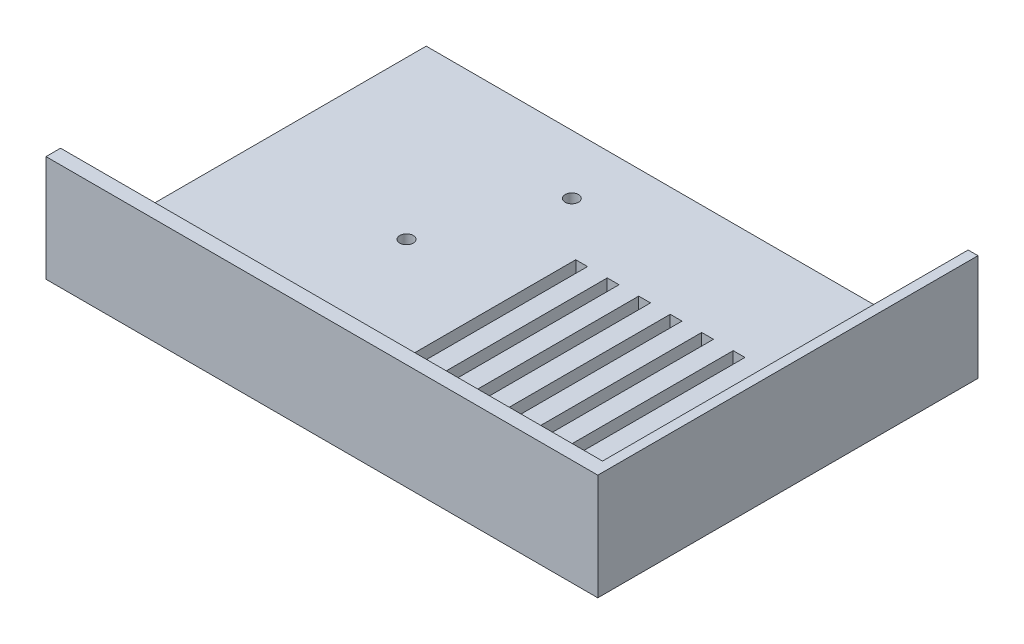
SolidWorks part; units mm, degrees
ref_plane "Front Plane" through (0, 0, 0) normal (0, 0, 1) x (1, 0, 0)
ref_plane "Top Plane" through (0, 0, 0) normal (0, 1, 0) x (1, 0, 0)
ref_plane "Right Plane" through (0, 0, 0) normal (1, 0, 0) x (0, 0, -1)
sketch "Sketch1" plane through (0, 0, 0) normal (0, 1, 0) x (1, 0, 0)
  line L1 (-140.2, -96.6) -> (140.2, -96.6)
  line L2 (-140.2, -96.6) -> (-140.2, 96.6)
  line L3 (-140.2, 96.6) -> (140.2, 96.6)
  line L4 (140.2, -96.6) -> (140.2, 96.6)
  line L5 (-140.2, -96.6) -> (140.2, 96.6) construction
  line L6 (-140.2, 96.6) -> (140.2, -96.6) construction
  point P0 (0, 0)
  dimension "D1" = 280.4
  dimension "D2" = 193.2
extrude "Shell Block" add sketch "Sketch1" along normal blind 27
ref_plane "Shell Front" through (0, 27, 0) normal (0, 1, 0) x (1, 0, 0)
sketch "Sketch2" plane through (0, 27, 0) normal (0, 1, 0) x (1, 0, 0)
  line L1 (-137.7, -92.9) -> (137.7, -92.9)
  line L2 (-137.7, -92.9) -> (-137.7, 92.9)
  line L3 (-137.7, 92.9) -> (137.7, 92.9)
  line L4 (137.7, -92.9) -> (137.7, 92.9)
  line L5 (-137.7, -92.9) -> (137.7, 92.9) construction
  line L6 (-137.7, 92.9) -> (137.7, -92.9) construction
  point P0 (0, 0)
  dimension "D1" = 275.4
  dimension "D2" = 185.8
extrude "Front Opening" cut sketch "Sketch2" against normal blind 1.5
ref_plane "Under Lip" through (0, 25.5, 0) normal (0, 1, 0) x (1, 0, 0)
sketch "Sketch3" plane through (0, 25.5, 0) normal (0, 1, 0) x (1, 0, 0)
  line L1 (-137.7, -94.1) -> (137.7, -94.1)
  line L2 (-137.7, -94.1) -> (-137.7, 94.1)
  line L3 (-137.7, 94.1) -> (137.7, 94.1)
  line L4 (137.7, -94.1) -> (137.7, 94.1)
  line L5 (-137.7, -94.1) -> (137.7, 94.1) construction
  line L6 (-137.7, 94.1) -> (137.7, -94.1) construction
  point P0 (0, 0)
  dimension "D1" = 275.4
  dimension "D2" = 188.2
extrude "Display Pocket" cut sketch "Sketch3" against normal blind 22.5
ref_plane "Back Inner" through (0, 3, 0) normal (0, 1, 0) x (1, 0, 0)
sketch "Sketch4" plane through (0, 3, 0) normal (0, 1, 0) x (1, 0, 0)
  line L1 (66, 28) -> (69, 28)
  line L2 (66, 28) -> (66, 84)
  line L3 (66, 84) -> (69, 84)
  line L4 (69, 28) -> (69, 84)
  line L6 (66, -84) -> (69, -84)
  line L7 (66, -84) -> (66, -28)
  line L8 (66, -28) -> (69, -28)
  line L9 (69, -84) -> (69, -28)
  line L11 (74, 28) -> (77, 28)
  line L12 (74, 28) -> (74, 84)
  line L13 (74, 84) -> (77, 84)
  line L14 (77, 28) -> (77, 84)
  line L16 (74, -84) -> (77, -84)
  line L17 (74, -84) -> (74, -28)
  line L18 (74, -28) -> (77, -28)
  line L19 (77, -84) -> (77, -28)
  line L21 (82, 28) -> (85, 28)
  line L22 (82, 28) -> (82, 84)
  line L23 (82, 84) -> (85, 84)
  line L24 (85, 28) -> (85, 84)
  line L26 (82, -84) -> (85, -84)
  line L27 (82, -84) -> (82, -28)
  line L28 (82, -28) -> (85, -28)
  line L29 (85, -84) -> (85, -28)
  line L31 (90, 28) -> (93, 28)
  line L32 (90, 28) -> (90, 84)
  line L33 (90, 84) -> (93, 84)
  line L34 (93, 28) -> (93, 84)
  line L36 (90, -84) -> (93, -84)
  line L37 (90, -84) -> (90, -28)
  line L38 (90, -28) -> (93, -28)
  line L39 (93, -84) -> (93, -28)
  line L41 (98, 28) -> (101, 28)
  line L42 (98, 28) -> (98, 84)
  line L43 (98, 84) -> (101, 84)
  line L44 (101, 28) -> (101, 84)
  line L46 (98, -84) -> (101, -84)
  line L47 (98, -84) -> (98, -28)
  line L48 (98, -28) -> (101, -28)
  line L49 (101, -84) -> (101, -28)
  line L51 (106, 28) -> (109, 28)
  line L52 (106, 28) -> (106, 84)
  line L53 (106, 84) -> (109, 84)
  line L54 (109, 28) -> (109, 84)
  line L56 (106, -84) -> (109, -84)
  line L57 (106, -84) -> (106, -28)
  line L58 (106, -28) -> (109, -28)
  line L59 (109, -84) -> (109, -28)
  line L61 (114, 28) -> (117, 28)
  line L62 (114, 28) -> (114, 84)
  line L63 (114, 84) -> (117, 84)
  line L64 (117, 28) -> (117, 84)
  line L66 (114, -84) -> (117, -84)
  line L67 (114, -84) -> (114, -28)
  line L68 (114, -28) -> (117, -28)
  line L69 (117, -84) -> (117, -28)
  line L71 (122, 28) -> (125, 28)
  line L72 (122, 28) -> (122, 84)
  line L73 (122, 84) -> (125, 84)
  line L74 (125, 28) -> (125, 84)
  line L76 (122, -84) -> (125, -84)
  line L77 (122, -84) -> (122, -28)
  line L78 (122, -28) -> (125, -28)
  line L79 (125, -84) -> (125, -28)
extrude "Vent Slots" cut sketch "Sketch4" against normal blind 4
sketch "Sketch5" plane through (0, 0, 0) normal (1, 0, 0) x (0, 0, -1)
  line L1 (-35, 5) -> (35, 5)
  line L2 (-35, 5) -> (-35, 21)
  line L3 (-35, 21) -> (35, 21)
  line L4 (35, 5) -> (35, 21)
extrude "Cable Exit (+X short side)" cut sketch "Sketch5" against normal blind 141.2
sketch "Sketch6" plane through (0, 3, 0) normal (0, 1, 0) x (1, 0, 0)
  circle A0 centre (-40, -45) radius 1.7
  circle A1 centre (-40, 45) radius 1.7
  circle A2 centre (40, -45) radius 1.7
  circle A3 centre (40, 45) radius 1.7
  circle A4 centre (-52, -15) radius 1.7
  circle A5 centre (-52, 15) radius 1.7
  circle A6 centre (52, -15) radius 1.7
  circle A7 centre (52, 15) radius 1.7
  circle A8 centre (-12, -82) radius 1.7
  circle A9 centre (-12, 82) radius 1.7
  circle A10 centre (12, -82) radius 1.7
  circle A11 centre (12, 82) radius 1.7
  circle A12 centre (-124, -12) radius 1.7
  circle A13 centre (-124, 12) radius 1.7
  circle A14 centre (124, -12) radius 1.7
  circle A15 centre (124, 12) radius 1.7
extrude "Bolt Holes" cut sketch "Sketch6" against normal blind 4
sketch "Sketch7" plane through (0, 0, 0) normal (0, 1, 0) x (1, 0, 0)
  line L1 (-200, -200) -> (0, -200)
  line L2 (-200, -200) -> (-200, 200)
  line L3 (-200, 200) -> (0, 200)
  line L4 (0, -200) -> (0, 200)
extrude "Keep one half (X)" cut sketch "Sketch7" against normal through all and the other way through all
sketch "Sketch8" plane through (0, 0, 0) normal (0, 1, 0) x (1, 0, 0)
  line L1 (-200, 0) -> (200, 0)
  line L2 (-200, 0) -> (-200, 200)
  line L3 (-200, 200) -> (200, 200)
  line L4 (200, 0) -> (200, 200)
extrude "Keep one quarter (Z)" cut sketch "Sketch8" against normal through all and the other way through all
equation "\"DispL\"= 274.2"
equation "\"DispW\"= 187.0"
equation "\"DispT\"= 20.0"
equation "\"Clr\"= 0.6"
equation "\"Wall\"= 2.5"
equation "\"BackT\"= 3.0"
equation "\"CableRoom\"= 4.0"
equation "\"LipW\"= 1.2"
equation "\"LipT\"= 1.5"
equation "\"CableW\"= 70.0"
equation "\"CableH\"= 16.0"
equation "\"BoltD\"= 3.4"
equation "\"ShellL\"= \"DispL\" + 2 * \"Clr\" + 2 * \"Wall\""
equation "\"ShellW\"= \"DispW\" + 2 * \"Clr\" + 2 * \"Wall\""
equation "\"ShellH\"= \"BackT\" + \"DispT\" + \"CableRoom\""
equation "\"D1@Sketch1\" = \"ShellL\""
equation "\"D2@Sketch1\" = \"ShellW\""
equation "\"D1@Shell Block\" = \"ShellH\""
equation "\"D1@Shell Front\" = \"ShellH\""
equation "\"D1@Sketch2\" = \"DispL\" + 2 * \"Clr\""
equation "\"D2@Sketch2\" = \"DispW\" + 2 * \"Clr\" - 2 * \"LipW\""
equation "\"D1@Front Opening\" = \"LipT\""
equation "\"D1@Under Lip\" = \"ShellH\" - \"LipT\""
equation "\"D1@Sketch3\" = \"DispL\" + 2 * \"Clr\""
equation "\"D2@Sketch3\" = \"DispW\" + 2 * \"Clr\""
equation "\"D1@Display Pocket\" = \"ShellH\" - \"LipT\" - \"BackT\""
equation "\"D1@Back Inner\" = \"BackT\""
